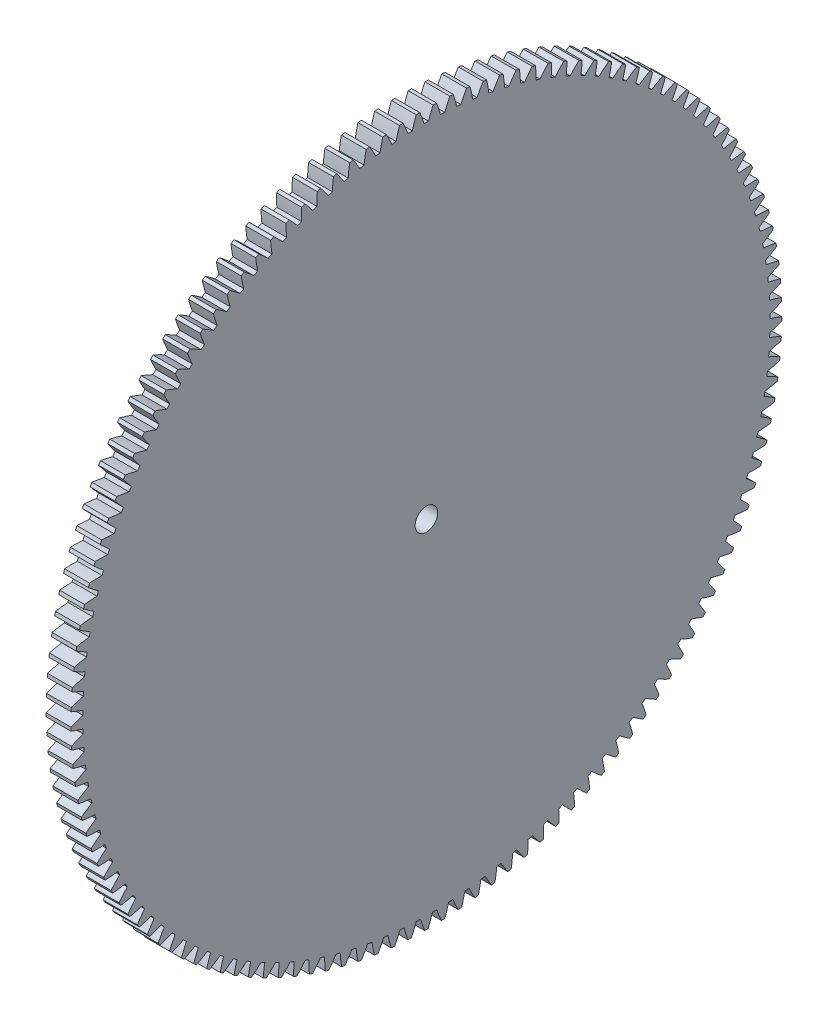
SolidWorks part; units mm, degrees
ref_plane "Plane1" through (0, 0, 0) normal (0, 0, 1) x (1, 0, 0)
ref_plane "Plane2" through (0, 0, 0) normal (0, 1, 0) x (1, 0, 0)
ref_plane "Plane3" through (0, 0, 0) normal (1, 0, 0) x (0, 0, -1)
sketch "HoldingSke" plane through (0, 0, 0) normal (0, 1, 0) x (1, 0, 0)
  line L0 (0, 0) -> (-0.9743, -1.0448)
  line L1 (-15, 0) -> (100, 0) construction
  line L2 (0, 0) -> (-2.1039, 2.3779)
  line L3 (0, 0) -> (-11.863, 4.5341)
  line L4 (0, 0) -> (-5.8897, 6.316)
  line L5 (0, 0) -> (-46.8476, -17.4728)
  line L6 (0, 0) -> (-2.7356, -1.8457)
  line L7 (-2.1039, 2.3779) -> (8.6586, 51.2059)
  line L8 (-76.2, 54.61) -> (-75.7, 54.61)
  line L9 (-71.009, 38.7566) -> (-53.1078, 45.2721)
  line L10 (-76.2, 71.12) -> (104.1128, 71.12)
  line L11 (0, 0) -> (-3.3, 0)
  line L12 (-76.2, 101.6) -> (-76.173, 101.6)
  line L13 (24.9733, 27.94) -> (52.9518, 28.4284)
  line L14 (24.9733, 27.94) -> (24.9743, 27.94)
  line L15 (24.9733, 27.94) -> (100.4006, 29.5858)
  line L16 (-63.627, -0.7) -> (-12.827, -0.7)
  circle A0 centre (0, 0) radius 1.5
  circle A1 centre (0, 0) radius 37.5
  circle A2 centre (0, 0) radius 37.5
  circle A3 centre (0, 0) radius 1.5
  dimension "Num_teeth" = 133
  dimension "Pitch_radius" = 180.3128
  dimension "Width" = 3.3
  dimension "Thickness" = 3.3
sketch "BasProSke" plane through (0, 0, 0) normal (0, 1, 0) x (1, 0, 0)
  line L0 (-10, 0) -> (60, 0) construction
  line L1 (0, 0) -> (0, 47.25)
  line L2 (0, 0) -> (3.3, 0)
  line L3 (3.3, 0) -> (3.3, 47.25)
  line L4 (3.3, 47.25) -> (0, 47.25)
  dimension "Thickness" = 3.3
  dimension "Diameter" = 94.5
revolve "Base-Revolve" add sketch "BasProSke" angle 360 about L0
sketch "TooCutSke" plane through (0, 0, 0) normal (1, 0, 0) x (0, 0, -1)
  line L1 (0, 0) -> (0, 107) construction
  line L2 (0, 0) -> (-0.597, 46.5462) construction
  line L3 (0, 0) -> (-2.1988, 93.0686) construction
  line L4 (-0.597, 46.5462) -> (-1.0994, 46.5343) construction
  arc A0 (0.2867, 45.6731) -> (-0.2867, 45.6731) centre (0, 0) ccw
  arc A1 (0.891, 47.267) -> (-0.891, 47.267) centre (0, 0) ccw
  circle A2 centre (0, 0) radius 46.55 construction
  circle A3 centre (0, 0) radius 43.7427 construction
  arc A4 (-0.2867, 45.6731) -> (-0.891, 47.267) centre (-17.9813, 39.876) ccw
  arc A5 (0.891, 47.267) -> (0.2867, 45.6731) centre (17.9813, 39.876) ccw
extrude "ToothCut" cut sketch "TooCutSke" along normal through all
fillet "Breaks" [suppressed] radius 0.014 tangent propagation no
fillet "RootFillets" [suppressed] radius 0.176
pattern_circular "TeethCuts" count 133 every 2.707 about axis through (-10, 0, 0) along (1, 0, 0) of "ToothCut", "RootFillets", "Breaks"
sketch "HubNeaOneSke" plane through (0, 0, 0) normal (-1, 0, 0) x (0, 0, 1)
  circle A0 centre (0, 0) radius 37.5
  dimension "Diameter" = 75
extrude "HubNearOne" [suppressed] add sketch "HubNeaOneSke" along normal blind 46.7001
sketch "HubNeaBotSke" plane through (0, 0, 0) normal (-1, 0, 0) x (0, 0, 1)
  circle A0 centre (0, 0) radius 37.5
  dimension "Diameter" = 75
extrude "HubNearBoth" [suppressed] add sketch "HubNeaBotSke" along normal blind 23.35
ref_plane "FarPln" through (3.3, 0, 0) normal (1, 0, 0) x (0, 0, -1)
sketch "HubFarSke" plane through (3.3, 0, 0) normal (1, 0, 0) x (0, 0, -1)
  circle A0 centre (0, 0) radius 37.5
  dimension "Diameter" = 75
extrude "HubFar" [suppressed] add sketch "HubFarSke" along normal blind 23.35
sketch "BorSke" plane through (0, 0, 0) normal (1, 0, 0) x (0, 0, -1)
  circle A0 centre (0, 0) radius 1.5
  dimension "Diameter" = 3
extrude "Bore" cut sketch "BorSke" along normal mid plane 100.0001
sketch "KeySke" plane through (0, 0, 0) normal (1, 0, 0) x (0, 0, -1)
  line L0 (-0.6, 0) -> (-0.6, 2)
  line L1 (-0.6, 2) -> (0.6, 2)
  line L2 (0.6, 2) -> (0.6, 0)
  line L3 (0, 0) -> (0, 34) construction
  line L4 (-0.6, 0) -> (0.6, 0)
  dimension "Width" = 1.2
extrude "Keyway" [suppressed] cut sketch "KeySke" along normal mid plane 100.0001
pattern_circular "Keyway2" [suppressed] count 2 every 90 about axis through (-10, 0, 0) along (1, 0, 0) reverse direction yes
equation "' \"Module@HoldingSke\" = 6.35"
equation "' \"Num_teeth@HoldingSke\" = 12"
equation "' \"Ap@HoldingSke\" =  20"
equation "' \"Ap@HoldingSke\" = 20"
equation "' \"Width@HoldingSke\" = 0.5 * 25.4"
equation "' \"Hub_dia@HoldingSke\"= 1 * 25.4"
equation "' \"Hub_dia@HoldingSke\" = 1 * 25.4"
equation "' \"Overall_len@HoldingSke\" = 1.0 * 25.4"
equation "' \"Bore@HoldingSke\" = 0.75 * 25.4"
equation "' \"T_dim@HoldingSke\" = 0.1 * 25.4"
equation "' \"Width@KeySke\" = 0.25 * 25.4"
equation "' \"Show_teeth@HoldingSke\" = 13"
equation "' \"Backlash@HoldingSke\" = 0.009 * 25.4"
equation "' \"Addendum_fac@HoldingSke\" = 1.0"
equation "' \"Dedendum_fac@HoldingSke\" = 1.25"
equation "' \"Dedendum_add@HoldingSke\" = 0.00005 * 25.4"
equation "' \"Clearance_fac@HoldingSke\" = 0.25"
equation "\"Pitch@HoldingSke\" = 1 / \"Module@HoldingSke\""
equation "\"Overcut_dia@TooCutSke\" = (\"Num_teeth@HoldingSke\" + 2 * \"Addendum_fac@HoldingSke\") / \"Pitch@HoldingSke\" + 0.002 * 25.4"
equation "\"Pitch_dia@TooCutSke\" = \"Num_teeth@HoldingSke\" / \"Pitch@HoldingSke\""
equation "\"Base_dia@TooCutSke\" = \"Num_teeth@HoldingSke\" / \"Pitch@HoldingSke\" * cos((\"Ap@HoldingSke\"  * 3.14159265 / 180))"
equation "\"Root_dia@TooCutSke\" = (\"Num_teeth@HoldingSke\" + 2) / \"Pitch@HoldingSke\" - 2 * (\"Addendum_fac@HoldingSke\" + \"Dedendum_fac@HoldingSke\") / \"Pitch@HoldingSke\" - \"Dedendum_add@HoldingSke\" * 2"
equation "\"Half_ang@TooCutSke\" = 180 / \"Num_teeth@HoldingSke\""
equation "\"Half_CT@TooCutSke\" = \"Num_teeth@HoldingSke\" / \"Pitch@HoldingSke\" * sin((3.14159265 / 2 / \"Num_teeth@HoldingSke\")) / 2 - 7 * \"Backlash@HoldingSke\" / 4"
equation "\"Flank_rad@TooCutSke\" = \"Num_teeth@HoldingSke\" / \"Pitch@HoldingSke\" / 5"
equation "\"Radius@RootFillets\" = \"Clearance_fac@HoldingSke\" / \"Pitch@HoldingSke\" + \"Dedendum_add@HoldingSke\""
equation "\"Break_rad@Breaks\" = 0.02 / \"Pitch@HoldingSke\""
equation "\"Thickness@HoldingSke\" = \"Width@HoldingSke\""
equation "\"OAL@HoldingSke\" = \"Thickness@HoldingSke\""
equation "\"MHD@HoldingSke\" = (\"Num_teeth@HoldingSke\" + 2) / \"Pitch@HoldingSke\" - 2 * (\"Addendum_fac@HoldingSke\" + \"Dedendum_fac@HoldingSke\")  / \"Pitch@HoldingSke\" - \"Dedendum_add@HoldingSke\" * 2"
equation "\"MBD@HoldingSke\" = (\"Num_teeth@HoldingSke\" + 2) / \"Pitch@HoldingSke\" - 2 * (\"Addendum_fac@HoldingSke\" + \"Dedendum_fac@HoldingSke\")  / \"Pitch@HoldingSke\" - \"Dedendum_add@HoldingSke\" * 2 - 0.002 * 25.4"
equation "\"MHD@HoldingSke\" = ((sgn( \"MHD@HoldingSke\" - \"Hub_dia@HoldingSke\" )-1)*( \"MHD@HoldingSke\" - \"Hub_dia@HoldingSke\" ))/-2+ \"Hub_dia@HoldingSke\""
equation "\"MBD@HoldingSke\" = ((sgn( \"MBD@HoldingSke\" - \"Bore@HoldingSke\" )-1)*( \"MBD@HoldingSke\" - \"Bore@HoldingSke\" ))/-2+ \"Bore@HoldingSke\""
equation "\"OAL@HoldingSke\" = ((sgn( \"OAL@HoldingSke\" - \"Overall_len@HoldingSke\" )+1)*( \"OAL@HoldingSke\" - \"Overall_len@HoldingSke\" ))/2 + \"Overall_len@HoldingSke\" + 0.000002 * 25.4"
equation "\"Num_teeth@TeethCuts\" = int( \"Show_teeth@HoldingSke\" ) + 1"
equation "\"Num_teeth@TeethCuts\" = ((sgn( \"Num_teeth@TeethCuts\" - \"Num_teeth@HoldingSke\" )-1)*( \"Num_teeth@TeethCuts\" - \"Num_teeth@HoldingSke\" ))/-2+ \"Num_teeth@HoldingSke\""
equation "\"Num_teeth@TeethCuts\" = ((sgn( \"Num_teeth@TeethCuts\" - 2.0)+1)*( \"Num_teeth@TeethCuts\" - 2.0))/2 +2.0"
equation "\"Angle@TeethCuts\" = 360.0 / \"Num_teeth@HoldingSke\""
equation "\"Diameter@BasProSke\" = (\"Num_teeth@HoldingSke\" + 2 * \"Addendum_fac@HoldingSke\") / \"Pitch@HoldingSke\""
equation "\"Thickness@BasProSke\"  = \"Thickness@HoldingSke\""
equation "' \"Fillet_rad@BasProSke\" =  \"Thickness@HoldingSke\" * 0.05"
equation "' \"Fillet_rad@BasProSke\" = \"Thickness@HoldingSke\" * 0.05"
equation "\"MHD@HoldingSke\" = ((sgn( \"MHD@HoldingSke\" - \"Root_dia@TooCutSke\" )-1)*( \"MHD@HoldingSke\" - \"Root_dia@TooCutSke\" ))/-2+ \"Root_dia@TooCutSke\""
equation "\"Diameter@HubNeaOneSke\" = \"MHD@HoldingSke\""
equation "\"Length@HubNearOne\" = \"OAL@HoldingSke\" - \"Thickness@BasProSke\""
equation "\"Diameter@HubNeaBotSke\" = \"MHD@HoldingSke\""
equation "\"Length@HubNearBoth\" = ( \"OAL@HoldingSke\" - \"Thickness@BasProSke\" ) / 2.0"
equation "\"Thickness@FarPln\" = \"Thickness@BasProSke\""
equation "\"Diameter@HubFarSke\" = \"MHD@HoldingSke\""
equation "\"Length@HubFar\" = ( \"OAL@HoldingSke\" - \"Thickness@BasProSke\" ) / 2.0"
equation "\"Diameter@BorSke\" = \"MBD@HoldingSke\""
equation "\"D1@Bore\" = \"OAL@HoldingSke\" * 2.0"
equation "\"D1@Keyway\" = \"OAL@HoldingSke\" * 2.0"
equation "\"Offset@KeySke\" = \"T_dim@HoldingSke\" + \"MBD@HoldingSke\" / 2.0"
